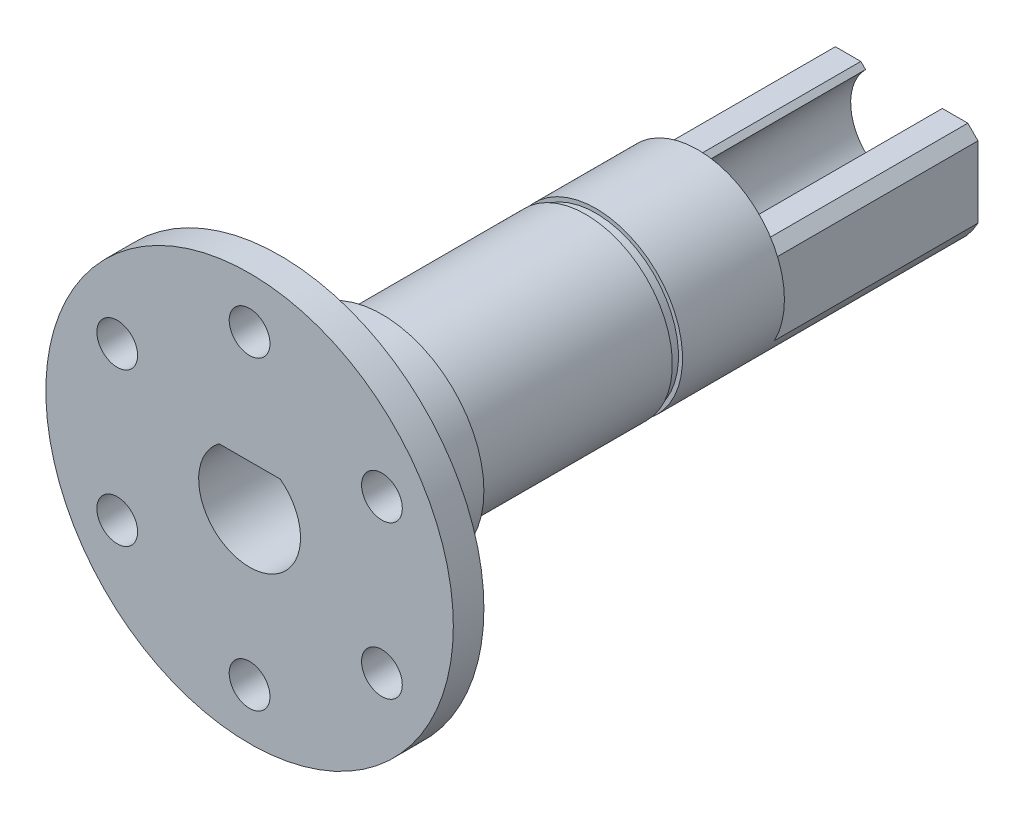
SolidWorks part; units mm, degrees
material "6061 合金"
ref_plane "前视基准面" through (0, 0, 0) normal (0, 0, 1) x (1, 0, 0)
ref_plane "上视基准面" through (0, 0, 0) normal (0, 1, 0) x (1, 0, 0)
ref_plane "右视基准面" through (0, 0, 0) normal (1, 0, 0) x (0, 0, -1)
sketch "草图1" plane through (0, 0, 0) normal (0, 0, 1) x (1, 0, 0)
  circle A0 centre (0, 0) radius 8.5
  dimension "D1" = 17
extrude "凸台-拉伸1" add sketch "草图1" along normal blind 33
sketch "草图2" plane through (0, 0, 33) normal (0, 0, 1) x (1, 0, 0)
  circle A0 centre (0, 0) radius 8.5
  dimension "D1" = 17
extrude "凸台-拉伸2" add sketch "草图2" along normal blind 11
sketch "草图3" plane through (0, 0, 44) normal (0, 0, 1) x (1, 0, 0)
  circle A0 centre (0, 0) radius 10
  dimension "D1" = 20
extrude "凸台-拉伸3" add sketch "草图3" along normal blind 10
chamfer "倒角2" distance 0.5 angle 45 1 edges at (8.5, 0, 0)
sketch "草图12" plane through (0, 0, 0) normal (1, 0, 0) x (0, 0, -1)
  line L0 (0, 0) -> (-44, 0) construction
  line L1 (-44, -8.5) -> (-44, 8.5) construction
  line L2 (-24, 8.1) -> (-24, 8.5)
  line L3 (-0.5, 8.5) -> (-44, 8.5) construction
  line L4 (-24, 8.1) -> (-23, 8.1)
  line L5 (-23, 8.1) -> (-23, 8.5)
  line L6 (-23, 8.5) -> (-24, 8.5)
  line L7 (0, -8) -> (0, 8) construction
  dimension "D1" = 0.4
  dimension "D2" = 1
  dimension "D3" = 23
revolve "切除-旋转1" cut sketch "草图12" angle 360 about L0
sketch "草图13" plane through (0, 0, 0) normal (0, 0, -1) x (-1, 0, 0)
  circle A0 centre (0, 0) radius 5
  dimension "D1" = 10
extrude "切除-拉伸1" cut sketch "草图13" against normal blind 20
sketch "草图14" plane through (0, 0, 54) normal (0, 0, 1) x (1, 0, 0)
  circle A0 centre (0, 0) radius 20
  circle A1 centre (0, 15) radius 2
  circle A2 centre (12.9904, 7.5) radius 2
  circle A3 centre (12.9904, -7.5) radius 2
  circle A4 centre (0, -15) radius 2
  circle A5 centre (-12.9904, -7.5) radius 2
  circle A6 centre (-12.9904, 7.5) radius 2
  point P0 (0, 0)
  point P15 (0, 0)
  dimension "D1" = 40
  dimension "D2" = 4
  dimension "D3" = 15
  dimension "D4" = 6
ref_plane "基准面1" through (0, 0, 0.5) normal (0, 0, -1) x (-1, 0, 0)
sketch "草图19" plane through (0, 0, 0.5) normal (0, 0, -1) x (-1, 0, 0)
  circle A0 centre (0, 0) radius 8.5
extrude "凸台-拉伸6" add sketch "草图19" along normal blind 7.5
sketch "草图20" plane through (0, 0, -7) normal (0, 0, -1) x (-1, 0, 0)
  circle A0 centre (0, 0) radius 5
  dimension "D1" = 10
extrude "切除-拉伸5" cut sketch "草图20" against normal blind 7.5
sketch "草图21" plane through (0, 0, 0) normal (0, 1, 0) x (1, 0, 0)
  line L0 (8.5, 7) -> (-8.5, 7) construction
  line L1 (8.5, -23) -> (8.5, 7) construction
  circle A0 centre (0, -3) radius 1.5
  dimension "D1" = 3
  dimension "D2" = 10
  dimension "D3" = 8.5
extrude "切除-拉伸6" cut sketch "草图21" against normal blind 16.5 and the other way blind 16.5
extrude "凸台-拉伸7" add sketch "草图14" along normal blind 3
sketch "草图23" plane through (0, 0, 20) normal (0, 0, -1) x (-1, 0, 0)
  circle A0 centre (0, 0) radius 5
extrude "凸台-拉伸8" add sketch "草图23" along normal blind 7
sketch "草图24" plane through (0, 0, 57) normal (0, 0, 1) x (1, 0, 0)
  circle A0 centre (0, 0) radius 5
  dimension "D1" = 10
extrude "切除-拉伸7" cut sketch "草图24" against normal blind 44
sketch "草图31" plane through (0, 0, 57) normal (0, 0, 1) x (1, 0, 0)
  circle A0 centre (0, 0) radius 5
  circle A1 centre (0, 0) radius 7
  dimension "D1" = 14
  dimension "D2" = 10
extrude "凸台-拉伸10" add sketch "草图31" along normal blind 20
ref_axis "基准轴1" through (0, 13.3188, 3) along (0, -1, 0)
sketch "草图32" plane through (0, 0, -7) normal (0, 0, -1) x (-1, 0, 0)
  line L0 (-3, 4) -> (3, 4)
  arc A8 (3, 4) -> (-3, 4) centre (0, 0) ccw
  dimension "D1" = 4
extrude "凸台-拉伸11" add sketch "草图32" against normal blind 84
sketch "草图33" plane through (0, 4, 0) normal (0, -1, 0) x (1, 0, 0)
  circle A0 centre (0, 3) radius 1.5 construction
  circle A1 centre (0, 3) radius 1.5
extrude "切除-拉伸8" cut sketch "草图33" against normal blind 26
ref_plane "基准面2" through (0, 0, 74) normal (0, 0, 1) x (1, 0, 0)
sketch "草图35" plane through (0, 0, 74) normal (0, 0, 1) x (1, 0, 0)
  circle A0 centre (0, 0) radius 13
  circle A1 centre (0, 0) radius 7
extrude "凸台-拉伸12" add sketch "草图35" against normal blind 3
sketch "草图36" plane through (0, 0, 74) normal (0, 0, 1) x (1, 0, 0)
  circle A0 centre (0, 0) radius 10 construction
  circle A1 centre (0, 10) radius 1.5
  circle A2 centre (8.6603, 5) radius 1.5
  circle A3 centre (8.6603, -5) radius 1.5
  circle A4 centre (0, -10) radius 1.5
  circle A5 centre (-8.6603, -5) radius 1.5
  circle A6 centre (-8.6603, 5) radius 1.5
  point P17 (0, 0)
  dimension "D1" = 3
  dimension "D2" = 6
extrude "切除-拉伸10" cut sketch "草图36" against normal blind 3
sketch "草图38" plane through (0, 0, 77) normal (0, 0, 1) x (1, 0, 0)
  circle A0 centre (0, 0) radius 20
extrude "切除-拉伸12" cut sketch "草图38" against normal blind 20
sketch "草图39" plane through (0, 0, -7) normal (0, 0, -1) x (-1, 0, 0)
  line L0 (-7.5, 4) -> (7.5, 4)
  line L1 (7.5, 4) -> (7.5, 10.0107)
  line L2 (7.5, 10.0107) -> (-7.5, 10.0107)
  line L3 (-7.5, 10.0107) -> (-7.5, 4)
  circle A0 centre (0, 0) radius 8.5 construction
extrude "切除-拉伸13" cut sketch "草图39" against normal blind 20
sketch "草图40" plane through (0, 0, -7) normal (0, 0, -1) x (-1, 0, 0)
  line L0 (-7.5, 4) -> (-7.5, -4)
  line L1 (-7.5, -4) -> (-11.1906, -4)
  line L2 (-11.1906, -4) -> (-11.1906, 4)
  line L3 (-11.1906, 4) -> (-7.5, 4)
  line L4 (7.5, 4) -> (7.5, -4)
  line L5 (7.5, -4) -> (10.7135, -4)
  line L6 (10.7135, -4) -> (10.7135, 4)
  line L7 (10.7135, 4) -> (7.5, 4)
  arc A0 (-7.5, 4) -> (7.5, 4) centre (0, 0) ccw construction
extrude "切除-拉伸14" cut sketch "草图40" against normal blind 20
sketch "草图42" plane through (0, 0, -7) normal (0, 0, -1) x (-1, 0, 0)
  line L0 (-9.9614, -7) -> (9.4693, -7)
  line L1 (-7.5, 4) -> (-3, 4) construction
  line L2 (-9.9614, -7) -> (-9.9614, -10.4416)
  line L3 (-9.9614, -10.4416) -> (9.4693, -10.4416)
  line L4 (9.4693, -10.4416) -> (9.4693, -7)
  dimension "D1" = 11
extrude "切除-拉伸16" cut sketch "草图42" against normal blind 20
chamfer "倒角5" distance 1 angle 45 2 edges at (7.5, 4, 3) (-7.5, 4, 3)
chamfer "倒角6" distance 1 angle 45 2 edges at (-3, 4, 3) (3, 4, 3) first distance on face at (-4.75, 4, 3) first distance on face at (4.75, 4, 3)
